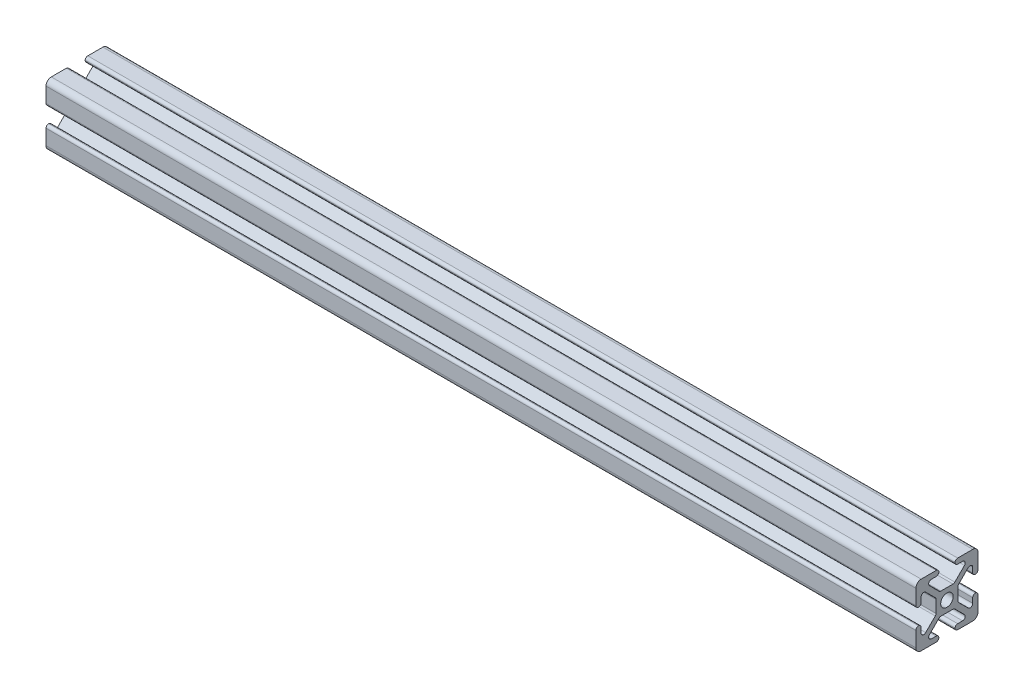
SolidWorks part; units mm, degrees
ref_plane "Front Plane" through (0, 0, 0) normal (1, 0, 0) x (0, 1, 0)
ref_plane "Top Plane" through (0, 0, 0) normal (0, 0, 1) x (0, 1, 0)
ref_plane "Right Plane" through (0, 0, 0) normal (0, 1, 0) x (-1, 0, 0)
sketch "Sketch1" plane through (0, 0, 0) normal (1, 0, 0) x (0, 1, 0)
  line L0 (0, 0) -> (0, 12.5) construction
  line L1 (-12.5, -12.5) -> (12.5, -12.5)
  line L2 (-12.5, -12.5) -> (-12.5, 12.5)
  line L3 (-12.5, 12.5) -> (12.5, 12.5)
  line L4 (12.5, -12.5) -> (12.5, 12.5)
  line L5 (-12.5, -12.5) -> (12.5, 12.5) construction
  line L6 (-12.5, 12.5) -> (12.5, -12.5) construction
  line L7 (-3.25, 12.5) -> (-3.25, 10.37)
  line L8 (-3.25, 10.37) -> (-8.8639, 10.37)
  line L9 (-8.8639, 10.37) -> (-2.8739, 4.38)
  line L10 (-2.8739, 4.38) -> (2.8739, 4.38)
  line L11 (8.8639, 10.37) -> (2.8739, 4.38)
  line L12 (3.25, 10.37) -> (8.8639, 10.37)
  line L13 (3.25, 12.5) -> (3.25, 10.37)
  line L14 (12.5, -3.25) -> (10.37, -3.25)
  line L15 (10.37, -3.25) -> (10.37, -8.8639)
  line L16 (10.37, -8.8639) -> (4.38, -2.8739)
  line L17 (4.38, 2.8739) -> (4.38, -2.8739)
  line L18 (10.37, 8.8639) -> (4.38, 2.8739)
  line L19 (10.37, 3.25) -> (10.37, 8.8639)
  line L20 (12.5, 3.25) -> (10.37, 3.25)
  line L21 (-3.25, -12.5) -> (-3.25, -10.37)
  line L22 (-3.25, -10.37) -> (-8.8639, -10.37)
  line L23 (-8.8639, -10.37) -> (-2.8739, -4.38)
  line L24 (2.8739, -4.38) -> (-2.8739, -4.38)
  line L25 (8.8639, -10.37) -> (2.8739, -4.38)
  line L26 (3.25, -10.37) -> (8.8639, -10.37)
  line L27 (3.25, -12.5) -> (3.25, -10.37)
  line L28 (-12.5, 3.25) -> (-10.37, 3.25)
  line L29 (-10.37, 3.25) -> (-10.37, 8.8639)
  line L30 (-10.37, 8.8639) -> (-4.38, 2.8739)
  line L31 (-4.38, -2.8739) -> (-4.38, 2.8739)
  line L32 (-10.37, -8.8639) -> (-4.38, -2.8739)
  line L33 (-10.37, -3.25) -> (-10.37, -8.8639)
  line L34 (-12.5, -3.25) -> (-10.37, -3.25)
  circle A0 centre (0, 0) radius 2.5
  point P0 (0, 0)
  point P15 (0, 4.38)
  dimension "D3" = 5
  dimension "D1" = 25
  dimension "D2" = 25
  dimension "D4" = 2.13
  dimension "D5" = 2.13
  dimension "D6" = 6.5
  dimension "D7" = 4.38
  dimension "D8" = 4
extrude "Boss-Extrude1" add sketch "Sketch1" along normal blind 350 contours L34 L2 L1 L21 L22 L23 L24 L25 L26 L27 L4 L14 L15 L16 L17 L18 L19 L20 L3 L13 L12 L11 L10 L9 L8 L7 L28 L29 L30 L31 L32 L33 A0 region at (0, -12.1464, -7.875)
fillet "Fillet1" radius 1.065 32 edges at (175, -10.37, -8.8639) (175, 2.8739, -4.38) (175, -2.8739, -4.38) (175, -4.38, 2.8739) (175, -4.38, -2.8739) (175, -2.8739, 4.38) (175, 2.8739, 4.38) (175, 4.38, 2.8739) (175, 4.38, -2.8739) (175, -8.8639, -10.37) (175, 8.8639, -10.37) (175, 10.37, -8.8639) (175, -10.37, 8.8639) (175, -8.8639, 10.37) (175, 10.37, 8.8639) (175, 8.8639, 10.37) (175, 12.5, 3.25) (175, -3.25, -12.5) (175, -10.37, 3.25) (175, 10.37, 3.25) (175, -10.37, -3.25) (175, -12.5, -3.25) (175, -12.5, 3.25) (175, 3.25, -10.37) (175, -3.25, -10.37) (175, 3.25, -12.5) (175, 10.37, -3.25) (175, 12.5, -3.25) (175, 3.25, 12.5) (175, 3.25, 10.37) (175, -3.25, 10.37) (175, -3.25, 12.5)
fillet "Fillet2" radius 2.13 4 edges at (175, 12.5, -12.5) (175, -12.5, -12.5) (175, 12.5, 12.5) (175, -12.5, 12.5)
sketch "Sketch2" plane through (350, 0, 0) normal (1, 0, 0) x (0, 1, 0)
  line L0 (10.37, -12.5) -> (4.315, -12.5)
  line L1 (10.37, -12.5) -> (4.315, -12.5)
  line L2 (4.315, -10.37) -> (6.2927, -10.37)
  line L3 (4.315, -10.37) -> (6.2927, -10.37)
  line L4 (7.0458, -8.5519) -> (3.1858, -4.6919)
  line L5 (7.0458, -8.5519) -> (3.1858, -4.6919)
  line L6 (2.4327, -4.38) -> (-2.4327, -4.38)
  line L7 (2.4327, -4.38) -> (-2.4327, -4.38)
  line L8 (-3.1858, -4.6919) -> (-7.0458, -8.5519)
  line L9 (-3.1858, -4.6919) -> (-7.0458, -8.5519)
  line L10 (-6.2927, -10.37) -> (-4.315, -10.37)
  line L11 (-6.2927, -10.37) -> (-4.315, -10.37)
  line L12 (-4.315, -12.5) -> (-10.37, -12.5)
  line L13 (-4.315, -12.5) -> (-10.37, -12.5)
  line L14 (-12.5, -10.37) -> (-12.5, -4.315)
  line L15 (-12.5, -10.37) -> (-12.5, -4.315)
  line L16 (-10.37, -4.315) -> (-10.37, -6.2927)
  line L17 (-10.37, -4.315) -> (-10.37, -6.2927)
  line L18 (-8.5519, -7.0458) -> (-4.6919, -3.1858)
  line L19 (-8.5519, -7.0458) -> (-4.6919, -3.1858)
  line L20 (-4.38, -2.4327) -> (-4.38, 2.4327)
  line L21 (-4.38, -2.4327) -> (-4.38, 2.4327)
  line L22 (-4.6919, 3.1858) -> (-8.5519, 7.0458)
  line L23 (-4.6919, 3.1858) -> (-8.5519, 7.0458)
  line L24 (-10.37, 6.2927) -> (-10.37, 4.315)
  line L25 (-10.37, 6.2927) -> (-10.37, 4.315)
  line L26 (-12.5, 4.315) -> (-12.5, 10.37)
  line L27 (-12.5, 4.315) -> (-12.5, 10.37)
  line L28 (-10.37, 12.5) -> (-4.315, 12.5)
  line L29 (-10.37, 12.5) -> (-4.315, 12.5)
  line L30 (-4.315, 10.37) -> (-6.2927, 10.37)
  line L31 (-4.315, 10.37) -> (-6.2927, 10.37)
  line L32 (-7.0458, 8.5519) -> (-3.1858, 4.6919)
  line L33 (-7.0458, 8.5519) -> (-3.1858, 4.6919)
  line L34 (-2.4327, 4.38) -> (2.4327, 4.38)
  line L35 (-2.4327, 4.38) -> (2.4327, 4.38)
  line L36 (3.1858, 4.6919) -> (7.0458, 8.5519)
  line L37 (3.1858, 4.6919) -> (7.0458, 8.5519)
  line L38 (6.2927, 10.37) -> (4.315, 10.37)
  line L39 (6.2927, 10.37) -> (4.315, 10.37)
  line L40 (4.315, 12.5) -> (10.37, 12.5)
  line L41 (4.315, 12.5) -> (10.37, 12.5)
  line L42 (12.5, 10.37) -> (12.5, 4.315)
  line L43 (12.5, 10.37) -> (12.5, 4.315)
  line L44 (10.37, 4.315) -> (10.37, 6.2927)
  line L45 (10.37, 4.315) -> (10.37, 6.2927)
  line L46 (8.5519, 7.0458) -> (4.6919, 3.1858)
  line L47 (8.5519, 7.0458) -> (4.6919, 3.1858)
  line L48 (4.38, 2.4327) -> (4.38, -2.4327)
  line L49 (4.38, 2.4327) -> (4.38, -2.4327)
  line L50 (4.6919, -3.1858) -> (8.5519, -7.0458)
  line L51 (4.6919, -3.1858) -> (8.5519, -7.0458)
  line L52 (10.37, -6.2927) -> (10.37, -4.315)
  line L53 (10.37, -6.2927) -> (10.37, -4.315)
  line L54 (12.5, -4.315) -> (12.5, -10.37)
  line L55 (12.5, -4.315) -> (12.5, -10.37)
  arc A0 (10.37, -12.5) -> (12.5, -10.37) centre (10.37, -10.37) ccw
  circle A1 centre (0, 0) radius 2.5
  circle A2 centre (0, 0) radius 2.5
  arc A3 (10.37, -12.5) -> (12.5, -10.37) centre (10.37, -10.37) ccw
  arc A4 (3.25, -11.435) -> (4.315, -12.5) centre (4.315, -11.435) ccw
  arc A5 (3.25, -11.435) -> (4.315, -12.5) centre (4.315, -11.435) ccw
  arc A6 (4.315, -10.37) -> (3.25, -11.435) centre (4.315, -11.435) ccw
  arc A7 (4.315, -10.37) -> (3.25, -11.435) centre (4.315, -11.435) ccw
  arc A8 (6.2927, -10.37) -> (7.0458, -8.5519) centre (6.2927, -9.305) ccw
  arc A9 (6.2927, -10.37) -> (7.0458, -8.5519) centre (6.2927, -9.305) ccw
  arc A10 (3.1858, -4.6919) -> (2.4327, -4.38) centre (2.4327, -5.445) ccw
  arc A11 (3.1858, -4.6919) -> (2.4327, -4.38) centre (2.4327, -5.445) ccw
  arc A12 (-2.4327, -4.38) -> (-3.1858, -4.6919) centre (-2.4327, -5.445) ccw
  arc A13 (-2.4327, -4.38) -> (-3.1858, -4.6919) centre (-2.4327, -5.445) ccw
  arc A14 (-7.0458, -8.5519) -> (-6.2927, -10.37) centre (-6.2927, -9.305) ccw
  arc A15 (-7.0458, -8.5519) -> (-6.2927, -10.37) centre (-6.2927, -9.305) ccw
  arc A16 (-3.25, -11.435) -> (-4.315, -10.37) centre (-4.315, -11.435) ccw
  arc A17 (-3.25, -11.435) -> (-4.315, -10.37) centre (-4.315, -11.435) ccw
  arc A18 (-4.315, -12.5) -> (-3.25, -11.435) centre (-4.315, -11.435) ccw
  arc A19 (-4.315, -12.5) -> (-3.25, -11.435) centre (-4.315, -11.435) ccw
  arc A20 (-12.5, -10.37) -> (-10.37, -12.5) centre (-10.37, -10.37) ccw
  arc A21 (-12.5, -10.37) -> (-10.37, -12.5) centre (-10.37, -10.37) ccw
  arc A22 (-11.435, -3.25) -> (-12.5, -4.315) centre (-11.435, -4.315) ccw
  arc A23 (-11.435, -3.25) -> (-12.5, -4.315) centre (-11.435, -4.315) ccw
  arc A24 (-10.37, -4.315) -> (-11.435, -3.25) centre (-11.435, -4.315) ccw
  arc A25 (-10.37, -4.315) -> (-11.435, -3.25) centre (-11.435, -4.315) ccw
  arc A26 (-10.37, -6.2927) -> (-8.5519, -7.0458) centre (-9.305, -6.2927) ccw
  arc A27 (-10.37, -6.2927) -> (-8.5519, -7.0458) centre (-9.305, -6.2927) ccw
  arc A28 (-4.6919, -3.1858) -> (-4.38, -2.4327) centre (-5.445, -2.4327) ccw
  arc A29 (-4.6919, -3.1858) -> (-4.38, -2.4327) centre (-5.445, -2.4327) ccw
  arc A30 (-4.38, 2.4327) -> (-4.6919, 3.1858) centre (-5.445, 2.4327) ccw
  arc A31 (-4.38, 2.4327) -> (-4.6919, 3.1858) centre (-5.445, 2.4327) ccw
  arc A32 (-8.5519, 7.0458) -> (-10.37, 6.2927) centre (-9.305, 6.2927) ccw
  arc A33 (-8.5519, 7.0458) -> (-10.37, 6.2927) centre (-9.305, 6.2927) ccw
  arc A34 (-11.435, 3.25) -> (-10.37, 4.315) centre (-11.435, 4.315) ccw
  arc A35 (-11.435, 3.25) -> (-10.37, 4.315) centre (-11.435, 4.315) ccw
  arc A36 (-12.5, 4.315) -> (-11.435, 3.25) centre (-11.435, 4.315) ccw
  arc A37 (-12.5, 4.315) -> (-11.435, 3.25) centre (-11.435, 4.315) ccw
  arc A38 (-10.37, 12.5) -> (-12.5, 10.37) centre (-10.37, 10.37) ccw
  arc A39 (-10.37, 12.5) -> (-12.5, 10.37) centre (-10.37, 10.37) ccw
  arc A40 (-3.25, 11.435) -> (-4.315, 12.5) centre (-4.315, 11.435) ccw
  arc A41 (-3.25, 11.435) -> (-4.315, 12.5) centre (-4.315, 11.435) ccw
  arc A42 (-4.315, 10.37) -> (-3.25, 11.435) centre (-4.315, 11.435) ccw
  arc A43 (-4.315, 10.37) -> (-3.25, 11.435) centre (-4.315, 11.435) ccw
  arc A44 (-6.2927, 10.37) -> (-7.0458, 8.5519) centre (-6.2927, 9.305) ccw
  arc A45 (-6.2927, 10.37) -> (-7.0458, 8.5519) centre (-6.2927, 9.305) ccw
  arc A46 (-3.1858, 4.6919) -> (-2.4327, 4.38) centre (-2.4327, 5.445) ccw
  arc A47 (-3.1858, 4.6919) -> (-2.4327, 4.38) centre (-2.4327, 5.445) ccw
  arc A48 (2.4327, 4.38) -> (3.1858, 4.6919) centre (2.4327, 5.445) ccw
  arc A49 (2.4327, 4.38) -> (3.1858, 4.6919) centre (2.4327, 5.445) ccw
  arc A50 (7.0458, 8.5519) -> (6.2927, 10.37) centre (6.2927, 9.305) ccw
  arc A51 (7.0458, 8.5519) -> (6.2927, 10.37) centre (6.2927, 9.305) ccw
  arc A52 (3.25, 11.435) -> (4.315, 10.37) centre (4.315, 11.435) ccw
  arc A53 (3.25, 11.435) -> (4.315, 10.37) centre (4.315, 11.435) ccw
  arc A54 (4.315, 12.5) -> (3.25, 11.435) centre (4.315, 11.435) ccw
  arc A55 (4.315, 12.5) -> (3.25, 11.435) centre (4.315, 11.435) ccw
  arc A56 (12.5, 10.37) -> (10.37, 12.5) centre (10.37, 10.37) ccw
  arc A57 (12.5, 10.37) -> (10.37, 12.5) centre (10.37, 10.37) ccw
  arc A58 (11.435, 3.25) -> (12.5, 4.315) centre (11.435, 4.315) ccw
  arc A59 (11.435, 3.25) -> (12.5, 4.315) centre (11.435, 4.315) ccw
  arc A60 (10.37, 4.315) -> (11.435, 3.25) centre (11.435, 4.315) ccw
  arc A61 (10.37, 4.315) -> (11.435, 3.25) centre (11.435, 4.315) ccw
  arc A62 (10.37, 6.2927) -> (8.5519, 7.0458) centre (9.305, 6.2927) ccw
  arc A63 (10.37, 6.2927) -> (8.5519, 7.0458) centre (9.305, 6.2927) ccw
  arc A64 (4.6919, 3.1858) -> (4.38, 2.4327) centre (5.445, 2.4327) ccw
  arc A65 (4.6919, 3.1858) -> (4.38, 2.4327) centre (5.445, 2.4327) ccw
  arc A66 (4.38, -2.4327) -> (4.6919, -3.1858) centre (5.445, -2.4327) ccw
  arc A67 (4.38, -2.4327) -> (4.6919, -3.1858) centre (5.445, -2.4327) ccw
  arc A68 (8.5519, -7.0458) -> (10.37, -6.2927) centre (9.305, -6.2927) ccw
  arc A69 (8.5519, -7.0458) -> (10.37, -6.2927) centre (9.305, -6.2927) ccw
  arc A70 (11.435, -3.25) -> (10.37, -4.315) centre (11.435, -4.315) ccw
  arc A71 (11.435, -3.25) -> (10.37, -4.315) centre (11.435, -4.315) ccw
  arc A72 (12.5, -4.315) -> (11.435, -3.25) centre (11.435, -4.315) ccw
  arc A73 (12.5, -4.315) -> (11.435, -3.25) centre (11.435, -4.315) ccw
  dimension "D1" = 0
